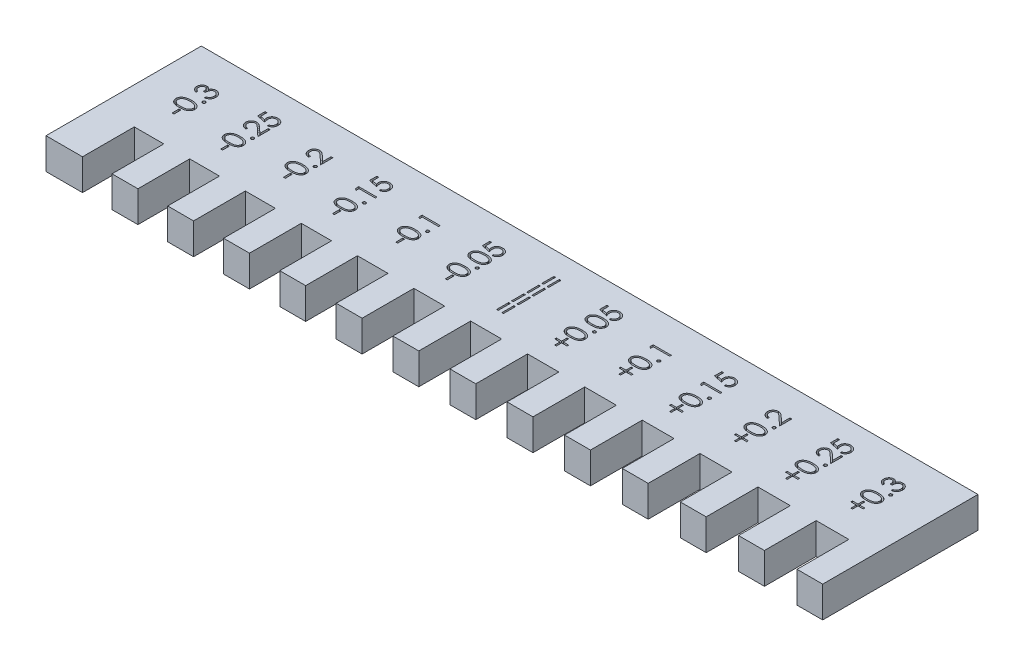
SolidWorks part; units mm, degrees
ref_plane "Front Plane" through (0, 0, 0) normal (0, 0, 1) x (1, 0, 0)
ref_plane "Top Plane" through (0, 0, 0) normal (0, 1, 0) x (1, 0, 0)
ref_plane "Right Plane" through (0, 0, 0) normal (1, 0, 0) x (0, 0, -1)
sketch "Sketch1" plane through (0, 0, 0) normal (0, 1, 0) x (1, 0, 0)
  line L1 (0, 0) -> (150, 0)
  line L2 (0, 0) -> (0, 30)
  line L3 (0, 30) -> (150, 30)
  line L4 (150, 0) -> (150, 30)
  dimension "D1" = 150
  dimension "D2" = 30
extrude "Boss-Extrude1" add sketch "Sketch1" along normal blind 6
sketch "Sketch2" plane through (0, 6, 0) normal (0, 1, 0) x (1, 0, 0)
  line L0 (75, 30) -> (75, 0) construction
  line L1 (150, 30) -> (0, 30) construction
  line L2 (0, 0) -> (150, 0) construction
  line L4 (72, 0) -> (78, 0)
  line L5 (72, 0) -> (72, 10)
  line L6 (72, 10) -> (78, 10)
  line L7 (78, 0) -> (78, 10)
  line L8 (83, 10) -> (89.05, 10)
  line L9 (83, 10) -> (83, 0)
  line L10 (83, 0) -> (89.05, 0)
  line L11 (89.05, 10) -> (89.05, 0)
  line L12 (94.05, 10) -> (100.15, 10)
  line L13 (94.05, 10) -> (94.05, 0)
  line L14 (94.05, 0) -> (100.15, 0)
  line L15 (100.15, 10) -> (100.15, 0)
  line L16 (105.15, 10) -> (111.3, 10)
  line L17 (105.15, 10) -> (105.15, 0)
  line L18 (105.15, 0) -> (111.3, 0)
  line L19 (111.3, 10) -> (111.3, 0)
  line L20 (67, 10) -> (61.05, 10)
  line L21 (67, 10) -> (67, 0)
  line L22 (67, 0) -> (61.05, 0)
  line L23 (61.05, 10) -> (61.05, 0)
  line L24 (56.05, 10) -> (50.15, 10)
  line L25 (56.05, 10) -> (56.05, 0)
  line L26 (56.05, 0) -> (50.15, 0)
  line L27 (50.15, 10) -> (50.15, 0)
  line L28 (45.15, 10) -> (39.3, 10)
  line L29 (45.15, 10) -> (45.15, 0)
  line L30 (45.15, 0) -> (39.3, 0)
  line L31 (39.3, 10) -> (39.3, 0)
  line L32 (34.3, 10) -> (28.5, 10)
  line L33 (34.3, 10) -> (34.3, 0)
  line L34 (34.3, 0) -> (28.5, 0)
  line L35 (28.5, 10) -> (28.5, 0)
  line L36 (23.5, 10) -> (17.75, 10)
  line L37 (23.5, 10) -> (23.5, 0)
  line L38 (23.5, 0) -> (17.75, 0)
  line L39 (17.75, 10) -> (17.75, 0)
  line L40 (116.3, 10) -> (122.5, 10)
  line L41 (116.3, 10) -> (116.3, 0)
  line L42 (116.3, 0) -> (122.5, 0)
  line L43 (122.5, 10) -> (122.5, 0)
  line L44 (127.5, 10) -> (133.75, 10)
  line L45 (127.5, 10) -> (127.5, 0)
  line L46 (127.5, 0) -> (133.75, 0)
  line L47 (133.75, 10) -> (133.75, 0)
  line L48 (138.75, 10) -> (145.05, 10)
  line L49 (138.75, 10) -> (138.75, 0)
  line L50 (138.75, 0) -> (145.05, 0)
  line L51 (145.05, 10) -> (145.05, 0)
  line L52 (12.75, 10) -> (7.05, 10)
  line L53 (12.75, 10) -> (12.75, 0)
  line L54 (12.75, 0) -> (7.05, 0)
  line L55 (7.05, 10) -> (7.05, 0)
  point P10 (75, 10)
  point P59 (83, 5)
  point P60 (83.4101, 10.3062)
  dimension "D1" = 6
  dimension "D2" = 10
  dimension "D3" = 5
  dimension "D4" = 5
  dimension "D5" = 5
  dimension "D6" = 5
  dimension "D7" = 5
  dimension "D8" = 5
  dimension "D9" = 5
  dimension "D10" = 5
  dimension "D11" = 5
  dimension "D12" = 5
  dimension "D13" = 5
  dimension "D14" = 5
  dimension "D15" = 5.95
  dimension "D16" = 5.9
  dimension "D17" = 5.85
  dimension "D18" = 5.8
  dimension "D19" = 5.75
  dimension "D20" = 5.7
  dimension "D21" = 6.05
  dimension "D22" = 6.1
  dimension "D23" = 6.15
  dimension "D24" = 6.2
  dimension "D25" = 6.25
  dimension "D26" = 6.3
extrude "Cut-Extrude1" cut sketch "Sketch2" against normal blind 10
sketch "Sketch3" plane through (0, 6, 0) normal (0, 1, 0) x (1, 0, 0)
  line L0 (145.05, 10) -> (138.75, 10) construction
  line L1 (141.9, 10) -> (141.9, 30) construction
  line L2 (150, 30) -> (0, 30) construction
  line L3 (130.625, 10) -> (130.625, 30) construction
  line L4 (133.75, 10) -> (127.5, 10) construction
  line L6 (122.5, 10) -> (116.3, 10) construction
  line L7 (119.4, 10) -> (119.4, 30) construction
  line L9 (111.3, 10) -> (105.15, 10) construction
  line L10 (108.225, 10) -> (108.225, 30) construction
  line L12 (100.15, 10) -> (94.05, 10) construction
  line L13 (97.1, 10) -> (97.1, 30) construction
  line L15 (89.05, 10) -> (83, 10) construction
  line L16 (86.025, 10) -> (86.025, 30) construction
  line L18 (78, 10) -> (72, 10) construction
  line L19 (75, 10) -> (75, 30) construction
  line L21 (67, 10) -> (61.05, 10) construction
  line L22 (64.025, 10) -> (64.025, 30) construction
  line L24 (56.05, 10) -> (50.15, 10) construction
  line L25 (53.1, 10) -> (53.1, 30) construction
  line L27 (45.15, 10) -> (39.3, 10) construction
  line L28 (42.225, 10) -> (42.225, 30) construction
  line L30 (34.3, 10) -> (28.5, 10) construction
  line L31 (31.4, 10) -> (31.4, 30) construction
  line L33 (23.5, 10) -> (17.75, 10) construction
  line L34 (20.625, 10) -> (20.625, 30) construction
  line L36 (12.75, 10) -> (7.05, 10) construction
  line L37 (9.9, 10) -> (9.9, 30) construction
  text T0 "===="
  text T1 "+0.05"
  text T2 "+0.1\r\n"
  text T3 "+0.15"
  text T4 "+0.2"
  text T5 "+0.25"
  text T6 "+0.3"
  text T7 "-0.05"
  text T8 "-0.1"
  text T9 "-0.15"
  text T10 "-0.2"
  text T11 "-0.25"
  text T12 "-0.3"
extrude "Cut-Extrude2" cut sketch "Sketch3" against normal blind 2
equation "\"boardThickness\"= 6"
equation "\"D1@Sketch2\"=\"boardThickness\""
equation "\"D15@Sketch2\"=\"boardThickness\" - 0.05"
equation "\"D16@Sketch2\"=\"boardThickness\" -0.1"
equation "\"D17@Sketch2\"=\"boardThickness\" - 0.15"
equation "\"D18@Sketch2\"=\"boardThickness\" -0.2"
equation "\"D19@Sketch2\"=\"boardThickness\"-0.25"
equation "\"D20@Sketch2\"=\"boardThickness\"-0.3"
equation "\"D21@Sketch2\"=\"boardThickness\"+0.05"
equation "\"D22@Sketch2\"=\"boardThickness\"+0.1"
equation "\"D23@Sketch2\"=\"boardThickness\" +0.15"
equation "\"D24@Sketch2\"=\"boardThickness\"+0.2"
equation "\"D25@Sketch2\"=\"boardThickness\"+0.25"
equation "\"D26@Sketch2\"=\"boardThickness\"+0.3"
